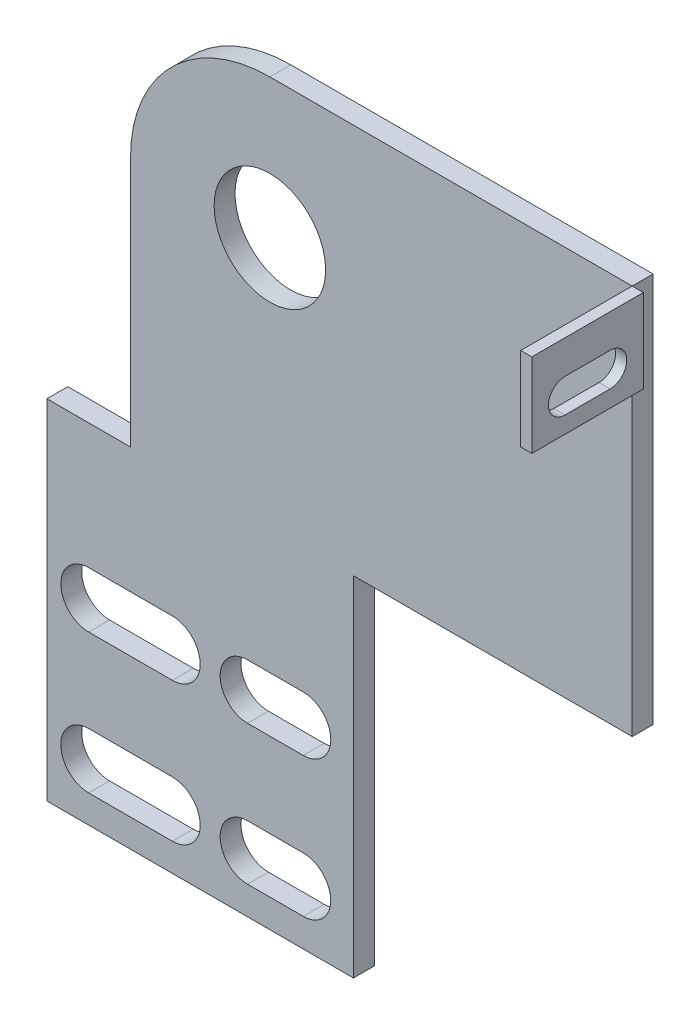
SolidWorks part; units mm, degrees
ref_plane "Front Plane" through (0, 0, 0) normal (0, 0, 1) x (1, 0, 0)
ref_plane "Top Plane" through (0, 0, 0) normal (0, 1, 0) x (1, 0, 0)
ref_plane "Right Plane" through (0, 0, 0) normal (1, 0, 0) x (0, 0, -1)
sketch "Sketch1" plane through (0, 0, 0) normal (0, 0, 1) x (1, 0, 0)
  line L1 (0, 0) -> (133.35, 0)
  line L2 (0, 0) -> (0, 168.275)
  line L3 (0, 168.275) -> (133.35, 168.275)
  line L4 (133.35, 0) -> (133.35, 168.275)
  dimension "D1" = 133.35
  dimension "D2" = 168.275
extrude "Boss-Extrude1" add sketch "Sketch1" along normal blind 4.7625
sketch "Sketch2" plane through (0, 0, 0) normal (0, 0, 1) x (1, 0, 0)
  line L0 (0, 79.375) -> (19.05, 79.375)
  line L1 (0, 168.275) -> (0, 0) construction
  line L2 (19.05, 79.375) -> (19.05, 136.525)
  line L3 (133.35, 168.275) -> (0, 168.275) construction
  line L4 (50.8, 168.275) -> (133.35, 168.275)
  line L5 (133.35, 168.275) -> (133.35, 79.375)
  line L6 (133.35, 0) -> (133.35, 168.275) construction
  line L7 (133.35, 79.375) -> (69.85, 79.375)
  line L8 (69.85, 79.375) -> (69.85, 0)
  line L9 (0, 0) -> (133.35, 0) construction
  line L10 (69.85, 0) -> (0, 0)
  line L11 (0, 0) -> (0, 79.375)
  line L12 (9.525, 44.45) -> (28.575, 44.45) construction
  line L13 (9.525, 50.8) -> (28.575, 50.8)
  line L14 (9.525, 38.1) -> (28.575, 38.1)
  line L15 (9.525, 12.7) -> (28.575, 12.7) construction
  line L16 (9.525, 19.05) -> (28.575, 19.05)
  line L17 (9.525, 6.35) -> (28.575, 6.35)
  line L18 (45.72, 44.45) -> (58.42, 44.45) construction
  line L19 (45.72, 50.709) -> (58.42, 50.709)
  line L20 (45.72, 38.191) -> (58.42, 38.191)
  line L21 (45.72, 12.7) -> (58.42, 12.7) construction
  line L22 (45.72, 18.959) -> (58.42, 18.959)
  line L23 (45.72, 6.441) -> (58.42, 6.441)
  arc A0 (19.05, 136.525) -> (50.8, 168.275) centre (50.8, 136.525) cw
  circle A1 centre (50.8, 136.525) radius 12.7
  arc A2 (9.525, 50.8) -> (9.525, 38.1) centre (9.525, 44.45) ccw
  arc A3 (28.575, 38.1) -> (28.575, 50.8) centre (28.575, 44.45) ccw
  arc A4 (9.525, 19.05) -> (9.525, 6.35) centre (9.525, 12.7) ccw
  arc A5 (28.575, 6.35) -> (28.575, 19.05) centre (28.575, 12.7) ccw
  arc A6 (45.72, 50.709) -> (45.72, 38.191) centre (45.72, 44.45) ccw
  arc A7 (58.42, 38.191) -> (58.42, 50.709) centre (58.42, 44.45) ccw
  arc A8 (45.72, 18.959) -> (45.72, 6.441) centre (45.72, 12.7) ccw
  arc A9 (58.42, 6.441) -> (58.42, 18.959) centre (58.42, 12.7) ccw
  point P23 (19.05, 44.45)
  point P30 (19.05, 12.7)
  point P37 (52.07, 44.45)
  point P44 (52.07, 12.7)
  dimension "D4" = 25.4
  dimension "D5" = 31.75
  dimension "D6" = 6.35
  dimension "D12" = 6.259
  dimension "D1" = 19.05
  dimension "D2" = 63.5
  dimension "D3" = 88.9
  dimension "D7" = 19.05
  dimension "D8" = 12.7
  dimension "D9" = 19.05
  dimension "D10" = 12.7
  dimension "D11" = 44.45
  dimension "D13" = 45.72
extrude "Cut-Extrude1" cut sketch "Sketch2" along normal through all flip side to cut
ref_plane "Plane1" through (133.35, 0, 0) normal (1, 0, 0) x (0, 0, -1)
sketch "Sketch3" plane through (133.35, 0, 0) normal (1, 0, 0) x (0, 0, -1)
  line L0 (-22.5728, 156.845) -> (-12.3522, 156.845) construction
  line L1 (-4.7625, 168.275) -> (-30.1625, 168.275)
  line L2 (-4.7625, 168.275) -> (-4.7625, 149.225)
  line L3 (-4.7625, 149.225) -> (-30.1625, 149.225)
  line L4 (-30.1625, 168.275) -> (-30.1625, 149.225)
  line L5 (-22.5728, 160.655) -> (-12.3522, 160.655)
  line L6 (-22.5728, 153.035) -> (-12.3522, 153.035)
  arc A0 (-22.5728, 160.655) -> (-22.5728, 153.035) centre (-22.5728, 156.845) ccw
  arc A1 (-12.3522, 153.035) -> (-12.3522, 160.655) centre (-12.3522, 156.845) ccw
  point P7 (-17.4625, 156.845)
  point P12 (-17.4625, 168.275)
  dimension "D3" = 3.81
  dimension "D1" = 25.4
  dimension "D2" = 19.05
  dimension "D4" = 7.62
extrude "Boss-Extrude2" add sketch "Sketch3" along normal blind 2.54 separate body
